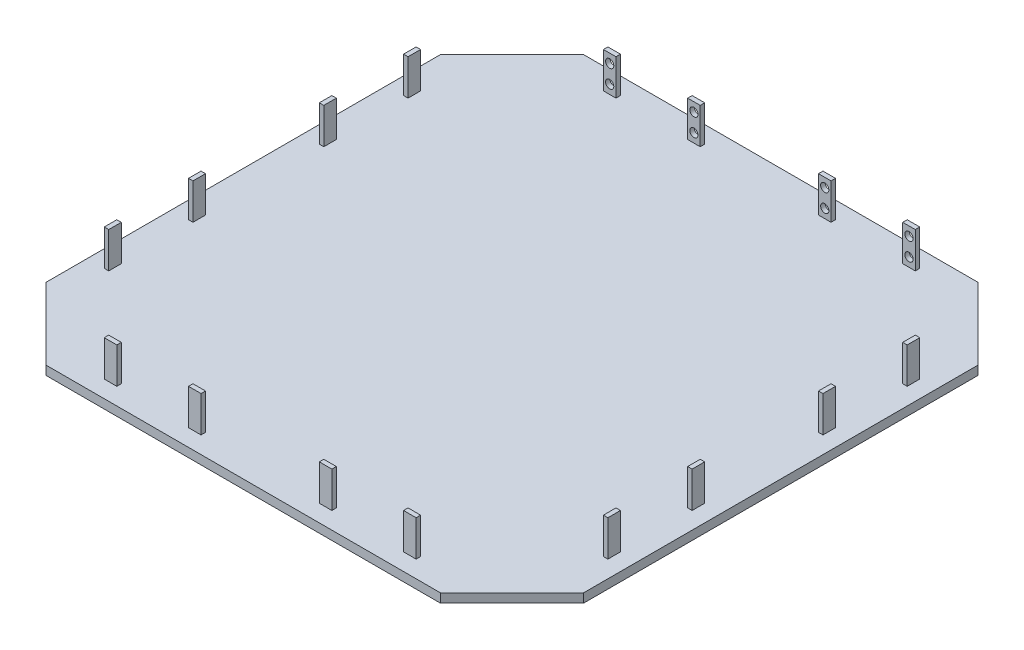
SolidWorks part; units mm, degrees
ref_plane "前视基准面" through (0, 0, 0) normal (0, 0, 1) x (1, 0, 0)
ref_plane "上视基准面" through (0, 0, 0) normal (0, 1, 0) x (1, 0, 0)
ref_plane "右视基准面" through (0, 0, 0) normal (1, 0, 0) x (0, 0, -1)
other "Configuration Table"
sketch "草图1" plane through (0, 0, 0) normal (0, 1, 0) x (1, 0, 0)
  line L0 (-110, 150) -> (-150, 110)
  line L1 (-150, 150) -> (150, 150)
  line L2 (-150, 150) -> (-150, -150)
  line L3 (-150, -150) -> (150, -150)
  line L4 (150, 150) -> (150, -150)
  line L5 (-150, 150) -> (150, -150) construction
  line L6 (-150, -150) -> (150, 150) construction
  line L7 (-40, -150) -> (-80, -150)
  line L8 (-40, -150) -> (-40, -110)
  line L9 (-40, -110) -> (-80, -110)
  line L10 (-80, -150) -> (-80, -110)
  line L11 (40, -110) -> (80, -110)
  line L12 (40, -110) -> (40, -150)
  line L13 (40, -150) -> (80, -150)
  line L14 (80, -110) -> (80, -150)
  line L15 (-150, 80) -> (-110, 80)
  line L16 (-150, 80) -> (-150, 40)
  line L17 (-150, 40) -> (-110, 40)
  line L18 (-110, 80) -> (-110, 40)
  line L19 (-150, -40) -> (-110, -40)
  line L20 (-150, -40) -> (-150, -80)
  line L21 (-150, -80) -> (-110, -80)
  line L22 (-110, -40) -> (-110, -80)
  line L23 (150, 80) -> (110, 80)
  line L24 (150, 80) -> (150, 40)
  line L25 (150, 40) -> (110, 40)
  line L26 (110, 80) -> (110, 40)
  line L27 (150, -40) -> (110, -40)
  line L28 (150, -40) -> (150, -80)
  line L29 (150, -80) -> (110, -80)
  line L30 (110, -40) -> (110, -80)
  line L31 (-80, 150) -> (-40, 150)
  line L32 (-80, 150) -> (-80, 110)
  line L33 (-80, 110) -> (-40, 110)
  line L34 (-40, 150) -> (-40, 110)
  line L35 (40, 150) -> (80, 150)
  line L36 (40, 150) -> (40, 110)
  line L37 (40, 110) -> (80, 110)
  line L38 (80, 150) -> (80, 110)
  line L39 (-110, -150) -> (-150, -110)
  line L40 (110, -150) -> (150, -110)
  line L41 (110, 150) -> (150, 110)
  line L43 (80, -140.5) -> (87, -140.5)
  line L44 (80, -140.5) -> (80, -138)
  line L45 (80, -138) -> (87, -138)
  line L46 (87, -140.5) -> (87, -138)
  line L47 (40, -140.5) -> (33, -140.5)
  line L48 (40, -140.5) -> (40, -138)
  line L49 (40, -138) -> (33, -138)
  line L50 (33, -140.5) -> (33, -138)
  line L51 (138, -80) -> (140.5, -80)
  line L52 (138, -80) -> (138, -87)
  line L53 (138, -87) -> (140.5, -87)
  line L54 (140.5, -80) -> (140.5, -87)
  line L55 (138, -40) -> (140.5, -40)
  line L56 (138, -40) -> (138, -33)
  line L57 (138, -33) -> (140.5, -33)
  line L58 (140.5, -40) -> (140.5, -33)
  line L59 (138, 40) -> (140.5, 40)
  line L60 (138, 40) -> (138, 33)
  line L61 (138, 33) -> (140.5, 33)
  line L62 (140.5, 40) -> (140.5, 33)
  line L63 (138, 80) -> (140.5, 80)
  line L64 (138, 80) -> (138, 87)
  line L65 (138, 87) -> (140.5, 87)
  line L66 (140.5, 80) -> (140.5, 87)
  line L67 (80, 138) -> (87, 138)
  line L68 (80, 138) -> (80, 140.5)
  line L69 (80, 140.5) -> (87, 140.5)
  line L70 (87, 138) -> (87, 140.5)
  line L71 (40, 138) -> (33, 138)
  line L72 (40, 138) -> (40, 140.5)
  line L73 (40, 140.5) -> (33, 140.5)
  line L74 (33, 138) -> (33, 140.5)
  line L75 (-40, 138) -> (-33, 138)
  line L76 (-40, 138) -> (-40, 140.5)
  line L77 (-40, 140.5) -> (-33, 140.5)
  line L78 (-33, 138) -> (-33, 140.5)
  line L79 (-80, 138) -> (-87, 138)
  line L80 (-80, 138) -> (-80, 140.5)
  line L81 (-80, 140.5) -> (-87, 140.5)
  line L82 (-87, 138) -> (-87, 140.5)
  line L83 (-140.5, 80) -> (-138, 80)
  line L84 (-140.5, 80) -> (-140.5, 87)
  line L85 (-140.5, 87) -> (-138, 87)
  line L86 (-138, 80) -> (-138, 87)
  line L87 (-140.5, 40) -> (-138, 40)
  line L88 (-140.5, 40) -> (-140.5, 33)
  line L89 (-140.5, 33) -> (-138, 33)
  line L90 (-138, 40) -> (-138, 33)
  line L91 (-140.5, -80) -> (-138, -80)
  line L92 (-140.5, -80) -> (-140.5, -87)
  line L93 (-140.5, -87) -> (-138, -87)
  line L94 (-138, -80) -> (-138, -87)
  line L95 (-140.5, -40) -> (-138, -40)
  line L96 (-140.5, -40) -> (-140.5, -33)
  line L97 (-140.5, -33) -> (-138, -33)
  line L98 (-138, -40) -> (-138, -33)
  line L99 (-80, -140.5) -> (-87, -140.5)
  line L100 (-80, -140.5) -> (-80, -138)
  line L101 (-80, -138) -> (-87, -138)
  line L102 (-87, -140.5) -> (-87, -138)
  line L103 (-40, -140.5) -> (-33, -140.5)
  line L104 (-40, -140.5) -> (-40, -138)
  line L105 (-40, -138) -> (-33, -138)
  line L106 (-33, -140.5) -> (-33, -138)
  point P0 (0, 0)
  dimension "D1" = 300
  dimension "D2" = 300
  dimension "D3" = 40
  dimension "D4" = 40
  dimension "D5" = 40
  dimension "D6" = 40
  dimension "D7" = 40
  dimension "D8" = 40
  dimension "D9" = 40
  dimension "D10" = 40
  dimension "D11" = 40
  dimension "D12" = 40
  dimension "D13" = 40
  dimension "D14" = 40
  dimension "D15" = 40
  dimension "D16" = 40
  dimension "D17" = 40
  dimension "D18" = 40
  dimension "D19" = 70
  dimension "D20" = 70
  dimension "D21" = 70
  dimension "D22" = 70
  dimension "D23" = 70
  dimension "D24" = 70
  dimension "D25" = 70
  dimension "D26" = 70
  dimension "D27" = 40
  dimension "D28" = 40
  dimension "D29" = 40
  dimension "D30" = 40
  dimension "D31" = 40
  dimension "D32" = 7
  dimension "D33" = 28
  dimension "D34" = 2.5
  dimension "D35" = 2.5
  dimension "D36" = 7
  dimension "D37" = 7
  dimension "D38" = 2.5
  dimension "D39" = 2.5
  dimension "D40" = 7
  dimension "D41" = 7
  dimension "D42" = 2.5
  dimension "D43" = 7
  dimension "D44" = 2.5
  dimension "D45" = 2.5
  dimension "D46" = 7
  dimension "D47" = 7
  dimension "D48" = 2.5
  dimension "D49" = 2.5
  dimension "D50" = 7
  dimension "D51" = 2.5
  dimension "D52" = 7
  dimension "D53" = 7
  dimension "D54" = 7
  dimension "D55" = 2.5
  dimension "D56" = 7
  dimension "D57" = 2.5
  dimension "D58" = 2.5
  dimension "D59" = 7
  dimension "D60" = 2.5
  dimension "D61" = 7
  dimension "D62" = 2.5
  dimension "D63" = 7
  dimension "D64" = 7
  dimension "D65" = 2.5
  dimension "D66" = 28
  dimension "D67" = 28
  dimension "D68" = 28
  dimension "D69" = 28
  dimension "D70" = 28
  dimension "D71" = 28
  dimension "D72" = 28
  dimension "D73" = 28
  dimension "D74" = 28
  dimension "D75" = 28
  dimension "D76" = 28
  dimension "D77" = 28
  dimension "D78" = 28
  dimension "D79" = 28
  dimension "D80" = 28
extrude "凸台-拉伸1" add sketch "草图1" along normal blind 5 contours L106 L103 L8 L3 L12 L47 L50 L49 L11 L14 L45 L46 L43 L40 L4 L29 L54 L53 L52 L30 L27 L56 L57 L58 L25 L62 L61 L60 L26 L23 L64 L65 L66 L41 L1 L38 L69 L70 L67 L37 L36 | L19 L98 L97 L96 | L90 L17 L88 L89 | L82 L79 L32 L81 | L75 L78 L77 L34 | L43 L46 L45 L14 | L14 L11 L12 L3 | L10 L3 L8 L9 | L27 L30 L29 L4 | L22 L19 L2 L21 | L18 L15 L2 L17 | L34 L1 L32 L33 | L38 L1 L36 L37 | L23 L26 L25 L4 | L101 L102 L99 L100 | L105 L106 L103 L104 | L94 L93 L92 L91 | L84 L85 L86 L83 | L67 L70 L69 L68 | L71 L74 L73 L72 | L64 L65 L66 L63 | L60 L61 L62 L59 | L56 L57 L58 L55 | L52 L53 L54 L51 | L47 L50 L49 L48 region at (0, 0, 0) region at (-60, 0, -130) region at (-130, 0, -60) region at (-83.5, 0, -139.25) region at (60, 0, -130) region at (-36.5, 0, -139.25) region at (-130, 0, 60) region at (-139.25, 0, -36.5) region at (-139.25, 0, 36.5) region at (130, 0, -60) region at (-60, 0, 130) region at (130, 0, 60) region at (60, 0, 130) region at (83.5, 0, 139.25)
extrude "凸台-拉伸2" add sketch "草图1<5>" along normal blind 25 contours L103 L106 L105 L8 | L50 L47 L12 L49 | L62 L25 L60 L61 | L67 L70 L69 L38 | L99 L102 L101 L100 | L45 L46 L43 L44 | L54 L53 L52 L51 | L58 L57 L56 L55 | L66 L65 L64 L63 | L73 L74 L71 L72 | L86 L85 L84 L83 | L88 L89 L90 L87 | L81 L82 L79 L80 | L77 L78 L75 L76 | L98 L97 L96 L95 | L94 L93 L92 L91 region at (83.5, 0, -139.25) region at (139.25, 0, -36.5) region at (-36.5, 0, 139.25) region at (36.5, 0, 139.25)
sketch "草图1<5>" plane through (0, 0, 0) normal (0, 1, 0) x (1, 0, 0) same geometry as "草图1"
sketch "草图2" plane through (0, 0, 140.5) normal (0, 0, 1) x (1, 0, 0)
  line L0 (-83.5, 25) -> (-83.5, 5) construction
  line L1 (-80, 25) -> (-87, 25) construction
  line L2 (-87, 5) -> (-80, 5) construction
  line L3 (-36.5, 25) -> (-36.5, 5) construction
  line L4 (-40, 25) -> (-33, 25) construction
  line L5 (36.5, 25) -> (36.5, 5) construction
  line L6 (40, 25) -> (33, 25) construction
  line L7 (33, 5) -> (40, 5) construction
  line L8 (83.5, 25) -> (83.5, 5) construction
  line L9 (80, 25) -> (87, 25) construction
  line L10 (87, 5) -> (80, 5) construction
  circle A0 centre (-83.5, 20) radius 2.3
  circle A1 centre (-83.5, 10) radius 2.3
  circle A2 centre (-36.5, 20) radius 2.3
  circle A3 centre (-36.5, 10) radius 2.3
  circle A4 centre (36.5, 20) radius 2.3
  circle A5 centre (36.5, 10) radius 2.3
  circle A6 centre (83.5, 20) radius 2.3
  circle A7 centre (83.5, 10) radius 2.3
  point P38 (0, 0)
  point P39 (0, 0)
  point P40 (0, 0)
  point P41 (0, 0)
  point P42 (0, 0)
  point P43 (0, 0)
  point P44 (0, 0)
  point P45 (0, 0)
  point P46 (0, 0)
  dimension "D1" = 10
  dimension "D2" = 10
  dimension "D3" = 10
  dimension "D4" = 10
  dimension "D5" = 5
  dimension "D6" = 5
  dimension "D7" = 5
  dimension "D8" = 5
sketch "草图3" plane through (140.5, 0, 0) normal (1, 0, 0) x (0, 0, -1)
  line L0 (-84, 25) -> (-84, 5) construction
  line L1 (33, 25) -> (33, 5) construction
  line L3 (-36, 25) -> (-36, 5) construction
  line L6 (36, 25) -> (36, 5) construction
  line L9 (83.5, 25) -> (83.5, 5) construction
  line L10 (80, 25) -> (87, 25) construction
  line L11 (87, 5) -> (80, 5) construction
  line L12 (-87, 25) -> (-87, 5) construction
  point P2 (-67.1674, 32.2245)
  point P5 (3.2915, 33.2737)
  point P26 (-130.3712, 32.816)
  dimension "D1" = 3
  dimension "D2" = 3
  dimension "D3" = 3
ref_plane "基准面1" through (87, 25, -140.5) normal (1, 0, 0) x (0, 0, -1)
sketch "草图6" plane through (0, 0, -140.5) normal (0, 0, -1) x (-1, 0, 0)
  line L0 (-83.5, 25) -> (-83.5, 5) construction
  line L1 (-36.5, 25) -> (-36.5, 5) construction
  line L2 (36.5, 25) -> (36.5, 5) construction
  line L3 (83.5, 25) -> (83.5, 5) construction
sketch "草图7" plane through (-140.5, 0, 0) normal (-1, 0, 0) x (0, 0, 1)
  line L0 (-83.5, 25) -> (-83.5, 5) construction
  line L1 (-36, 25) -> (-36, 5) construction
  line L2 (36.5, 25) -> (36.5, 5) construction
  line L3 (40, 25) -> (33, 25) construction
  line L4 (84, 25) -> (84, 5) construction
sketch "草图9" plane through (140.5, 0, 0) normal (1, 0, 0) x (0, 0, -1)
  line L0 (-84, 25) -> (-84, 5) construction
  line L1 (-36, 25) -> (-36, 5) construction
  line L2 (36, 25) -> (36, 5) construction
  line L3 (83.5, 25) -> (83.5, 5) construction
  circle A0 centre (-84, 20) radius 2.3
  circle A1 centre (-84, 10) radius 2.3
  circle A2 centre (-36, 20) radius 2.3
  circle A3 centre (-36, 10) radius 2.3
  circle A4 centre (36, 20) radius 2.3
  circle A5 centre (36, 10) radius 2.3
  circle A6 centre (83.5, 20) radius 2.3
  circle A7 centre (83.5, 10) radius 2.3
  point P24 (0, 0)
  dimension "D1" = 10
  dimension "D5" = 5
  dimension "D2" = 10
  dimension "D3" = 10
  dimension "D4" = 10
  dimension "D6" = 5
  dimension "D7" = 5
  dimension "D8" = 5
sketch "草图14" plane through (-140.5, 0, 0) normal (-1, 0, 0) x (0, 0, 1)
  circle A0 centre (-83.5, 20) radius 2.3
  circle A1 centre (-83.5, 10) radius 2.3
  circle A2 centre (-36, 20) radius 2.3
  circle A3 centre (-36, 10) radius 2.3
  circle A4 centre (36, 20) radius 2.3
  circle A5 centre (36, 10) radius 2.3
  circle A6 centre (84, 20) radius 2.3
  circle A7 centre (84, 10) radius 2.3
sketch "草图15" plane through (0, 0, -140.5) normal (0, 0, -1) x (-1, 0, 0)
  circle A0 centre (-83.5, 20) radius 2.3
  circle A1 centre (-83.5, 10) radius 2.3
  circle A2 centre (-36.5, 20) radius 2.3
  circle A3 centre (-36.5, 10) radius 2.3
  circle A4 centre (36.5, 10) radius 2.3
  circle A5 centre (36.5, 20) radius 2.3
  circle A6 centre (83.5, 20) radius 2.3
  circle A7 centre (83.5, 10) radius 2.3
  dimension "D1" = 10
  dimension "D2" = 5
  dimension "D3" = 5
extrude "切除-拉伸1" cut sketch "草图15" against normal blind 20
